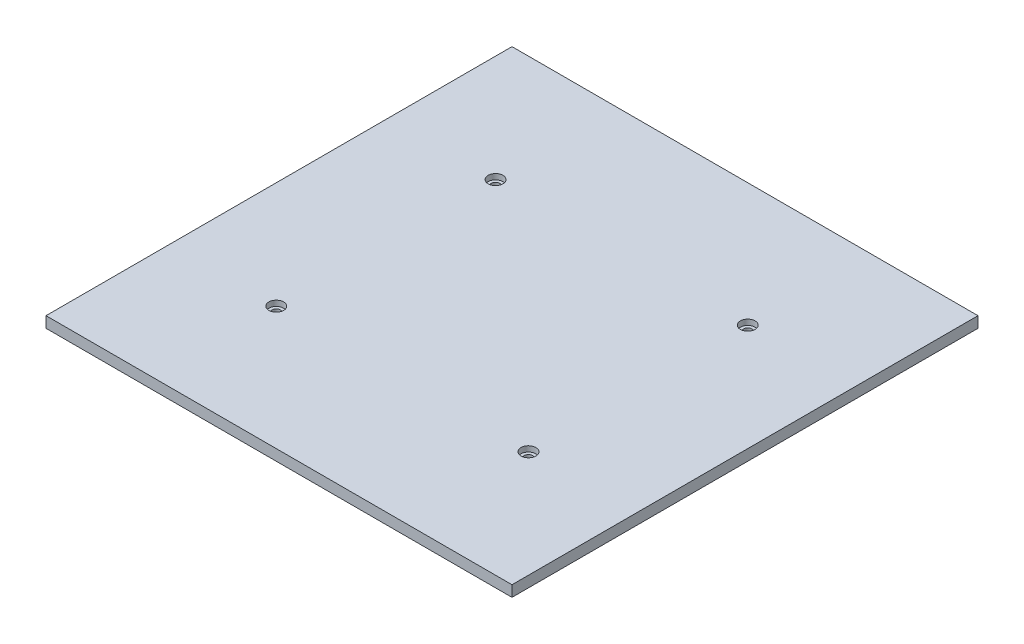
SolidWorks part; units mm, degrees
ref_plane "Front Plane" through (0, 0, 0) normal (0, 0, 1) x (1, 0, 0)
ref_plane "Top Plane" through (0, 0, 0) normal (0, 1, 0) x (1, 0, 0)
ref_plane "Right Plane" through (0, 0, 0) normal (1, 0, 0) x (0, 0, -1)
sketch "Sketch1" plane through (0, 0, 0) normal (0, 1, 0) x (1, 0, 0)
  line L0 (0, 0) -> (0, 85) construction
  line L1 (0, 85) -> (85, 85) construction
  line L3 (-85, -85) -> (85, -85)
  line L4 (-85, -85) -> (-85, 85)
  line L5 (-85, 85) -> (85, 85)
  line L6 (85, -85) -> (85, 85)
  line L7 (-85, -85) -> (85, 85) construction
  line L8 (-85, 85) -> (85, -85) construction
extrude "Boss-Extrude1" add sketch "Sketch1" along normal blind 4
sketch "Sketch2" plane through (0, 4, 0) normal (0, 1, 0) x (1, 0, 0)
  line L0 (0, 0) -> (31.4294, 0) construction
  line L1 (0, 0) -> (0, 40) construction
  line L2 (0, 40) -> (46, 40) construction
  circle A0 centre (46, 40) radius 1.6
  circle A1 centre (46, 40) radius 2.7
  circle A2 centre (-46, 40) radius 1.6
  circle A3 centre (-46, 40) radius 2.7
  circle A4 centre (46, -40) radius 1.6
  circle A5 centre (46, -40) radius 2.7
  circle A6 centre (-46, -40) radius 1.6
  circle A7 centre (-46, -40) radius 2.7
extrude "Cut-Extrude1" cut sketch "Sketch2" against normal up to next contours A6 | A2 | A4 | A0 region at (46, 4, -40) region at (-46, 4, -40) region at (46, 4, 40) region at (-46, 4, 40)
extrude "Cut-Extrude2" cut sketch "Sketch2<3>" against normal blind 2
sketch "Sketch2<3>" plane through (0, 4, 0) normal (0, 1, 0) x (1, 0, 0) same geometry as "Sketch2"
